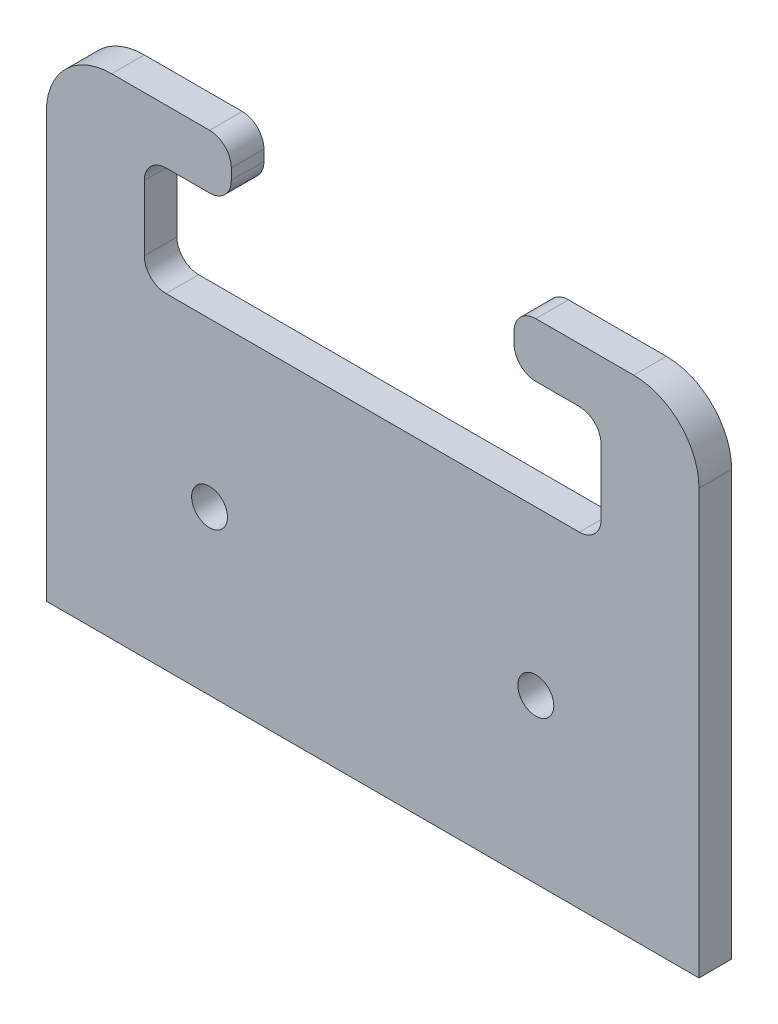
SolidWorks part; units mm, degrees
ref_plane "前视基准面" through (0, 0, 0) normal (0, 0, 1) x (1, 0, 0)
ref_plane "上视基准面" through (0, 0, 0) normal (0, 1, 0) x (1, 0, 0)
ref_plane "右视基准面" through (0, 0, 0) normal (1, 0, 0) x (0, 0, -1)
other "Configuration Table"
sketch "草图1" plane through (0, 0, 0) normal (0, 0, 1) x (1, 0, 0)
  line L0 (13, 22.5) -> (30, 22.5)
  line L1 (-30, 22.5) -> (-13, 22.5)
  line L2 (-30, 22.5) -> (-30, -22.5)
  line L3 (-30, -22.5) -> (30, -22.5)
  line L4 (30, 22.5) -> (30, -22.5)
  line L5 (-30, 22.5) -> (30, -22.5) construction
  line L6 (-30, -22.5) -> (30, 22.5) construction
  line L8 (13, 22.5) -> (13, 17.5)
  line L10 (-13, 22.5) -> (-13, 17.5)
  line L11 (21, 17.5) -> (13, 17.5)
  line L12 (21, 17.5) -> (21, 7.5)
  line L13 (21, 7.5) -> (-21, 7.5)
  line L14 (-21, 17.5) -> (-21, 7.5)
  line L15 (-13, 17.5) -> (-21, 17.5)
  point P0 (0, 0)
  dimension "D1" = 45
  dimension "D2" = 60
  dimension "D3" = 5
  dimension "D4" = 17
  dimension "D5" = 17
  dimension "D6" = 9
  dimension "D7" = 9
  dimension "D8" = 10
extrude "凸台-拉伸1" add sketch "草图1" along normal blind 3
fillet "圆角1" radius 6 2 edges at (30, 22.5, 1.5) (-30, 22.5, 1.5)
fillet "圆角2" radius 2 8 edges at (21, 17.5, 1.5) (21, 7.5, 1.5) (-21, 7.5, 1.5) (-21, 17.5, 1.5) (-13, 17.5, 1.5) (-13, 22.5, 1.5) (13, 17.5, 1.5) (13, 22.5, 1.5)
sketch "草图2" plane through (0, 0, 3) normal (0, 0, 1) x (1, 0, 0)
  line L0 (-30, -22.5) -> (30, -22.5) construction
  line L1 (-30, 16.5) -> (-30, -22.5) construction
  circle A0 centre (-15, -7.5) radius 1.65
  circle A1 centre (15, -7.5) radius 1.65
  dimension "D1" = 3.3
  dimension "D2" = 3.3
  dimension "D3" = 15
  dimension "D4" = 15
  dimension "D5" = 30
  dimension "D6" = 15
extrude "切除-拉伸1" cut sketch "草图2" against normal blind 5
